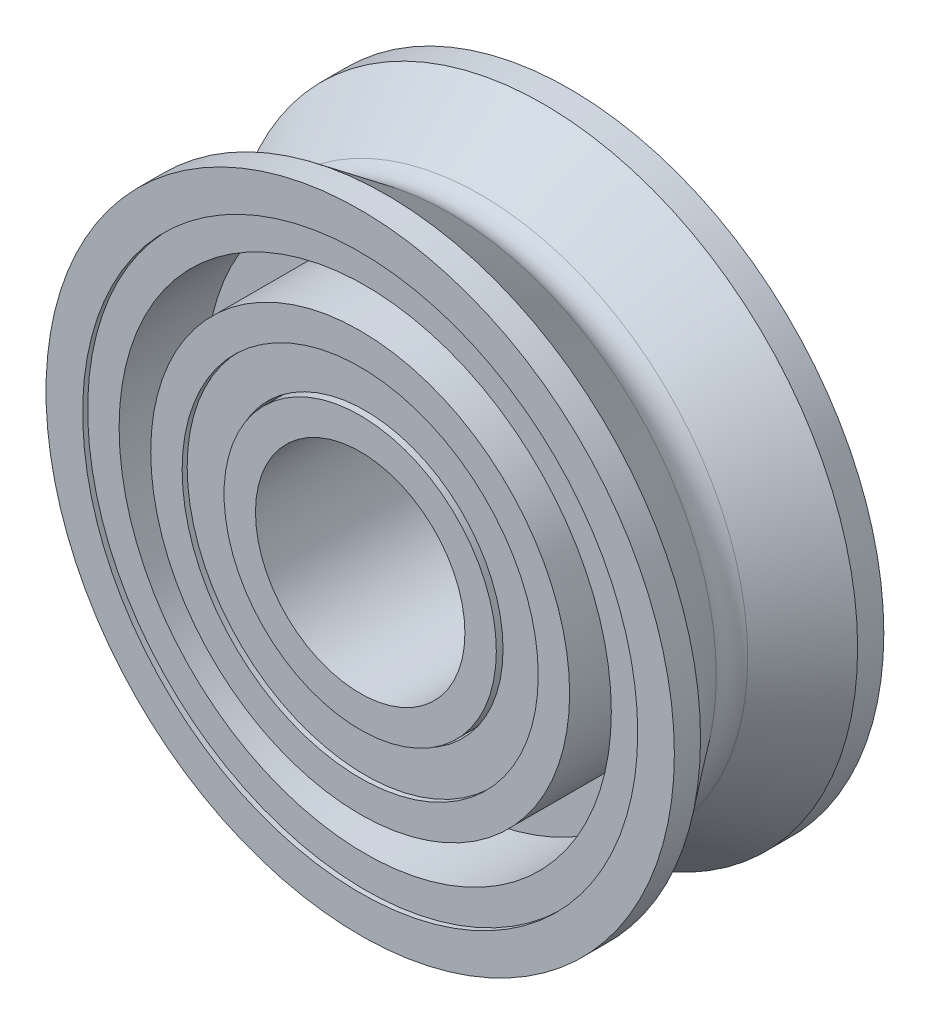
SolidWorks part; units mm, degrees
ref_plane "Front" through (0, 0, 0) normal (0, 0, 1) x (1, 0, 0)
ref_plane "Top" through (0, 0, 0) normal (0, 1, 0) x (1, 0, 0)
ref_plane "Right" through (0, 0, 0) normal (1, 0, 0) x (0, 0, -1)
sketch "Sketch1" plane through (0, 0, 0) normal (1, 0, 0) x (0, 0, -1)
  line L0 (1.1906, 4.7625) -> (1.5875, 4.7625)
  line L1 (-1.1906, 4.7625) -> (-1.5875, 4.7625)
  line L2 (-1.1906, 4.7625) -> (-0.2381, 4.0481)
  line L3 (1.5113, 2.6988) -> (1.5113, 2.0637)
  line L4 (1.5875, 1.5875) -> (-1.5875, 1.5875)
  line L5 (-1.5113, 2.0638) -> (-1.5113, 2.6988)
  line L6 (1.1906, 4.7625) -> (0.2381, 4.0481)
  line L7 (-1.5875, 4.2069) -> (-1.5113, 4.2069)
  line L8 (-1.5875, 0) -> (1.5875, 0) construction
  line L9 (-1.5113, 4.2069) -> (-1.5113, 3.7306)
  line L10 (1.5875, 4.7625) -> (1.5875, 4.2069)
  line L11 (1.5875, 4.2069) -> (1.5113, 4.2069)
  line L12 (-1.5113, 2.0638) -> (-1.5875, 2.0638)
  line L13 (-1.5875, 2.0638) -> (-1.5875, 1.5875)
  line L14 (0, 3.9688) -> (0, -3.9688) construction
  line L15 (1.5875, 2.0637) -> (1.5113, 2.0637)
  line L16 (1.5875, 2.0637) -> (1.5875, 1.5875)
  line L17 (-1.5875, 4.7625) -> (-1.5875, -4.7625) construction
  line L18 (-1.5113, 3.7306) -> (-0.1984, 3.7306)
  line L19 (-0.1984, 3.7306) -> (-0.1984, 3.175)
  line L20 (-0.1984, 3.175) -> (-1.5875, 3.175)
  line L21 (-1.5875, 4.2069) -> (-1.5875, 4.7625)
  line L22 (1.5113, 3.7306) -> (0.1984, 3.7306)
  line L23 (0.1984, 3.7306) -> (0.1984, 3.175)
  line L24 (0.1984, 3.175) -> (1.5875, 3.175)
  line L25 (1.5113, 4.2069) -> (1.5113, 3.7306)
  line L26 (-1.5113, 2.6988) -> (-1.5875, 2.6988)
  line L27 (-1.5875, 2.6988) -> (-1.5875, 3.175)
  line L28 (1.5875, 3.175) -> (1.5875, 2.6988)
  line L29 (1.5875, 2.6988) -> (1.5113, 2.6988)
  arc A0 (-0.2381, 4.0481) -> (0.2381, 4.0481) centre (0, 4.3656) ccw
  circle A1 centre (0, 4.3656) radius 0.3969 construction
  circle A2 centre (0, 0) radius 1.5875 construction
  circle A3 centre (0, 0) radius 2.0638 construction
  circle A4 centre (0, 0) radius 3.175 construction
  circle A5 centre (0, -4.3656) radius 0.3969 construction
  point P28 (-1.5875, 0)
  dimension "Rope Dia" = 0.7937
  dimension "Shaft Dia" = 3.175
  dimension "D1" = 4.1275
  dimension "D3" = 6.35
  dimension "Wd" = 3.175
  dimension "D8" = 0.3969
  dimension "Groove Dia" = 7.9375
  dimension "OD" = 9.525
  dimension "D6" = 0.0762
  dimension "D2" = 0.3969
revolve "Revolve1" add sketch "Sketch1" angle 360 about L8
sketch "Sketch2" plane through (0, 0, 0) normal (0, 0, 1) x (1, 0, 0)
  circle A0 centre (0, 0) radius 2.0638 construction
  circle A1 centre (0, 0) radius 2.0638
extrude "Cut-Extrude-Thin1" cut sketch "Sketch2" against normal through all and the other way through all thin thin type one direction wall 0.0254
equation "\"D1@Sketch1\" = \"Shaft Dia@Sketch1\" * 1.3"
equation "\"D3@Sketch1\" = \"Shaft Dia@Sketch1\" * 2"
equation "\"D8@Sketch1\" = \"Wd@Sketch1\" * .125"
equation "\"D2@Sketch1\" = \"D8@Sketch1\""
